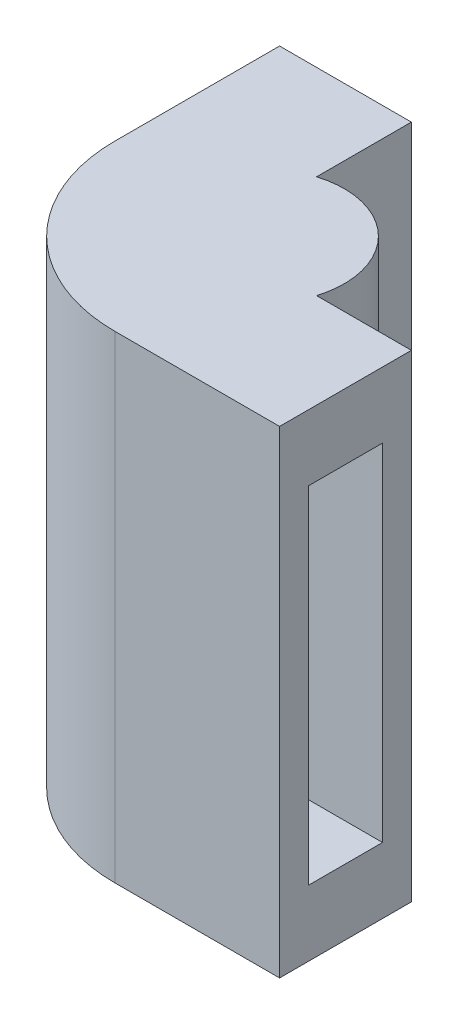
SolidWorks part; units mm, degrees
ref_plane "Front Plane" through (0, 0, 0) normal (0, 0, 1) x (1, 0, 0)
ref_plane "Top Plane" through (0, 0, 0) normal (0, 1, 0) x (1, 0, 0)
ref_plane "Right Plane" through (0, 0, 0) normal (1, 0, 0) x (0, 0, -1)
sketch "Sketch2" plane through (0, 0, 0) normal (0, 1, 0) x (1, 0, 0)
  line L0 (0, 10) -> (0, 20)
  line L1 (0, 20) -> (8, 20)
  line L2 (8, 20) -> (8, 14.2452)
  line L3 (0, 0) -> (22.3158, 22.3158) construction
  line L4 (10, 0) -> (22.3158, 0) construction
  line L5 (18, 8) -> (22.3158, 8) construction
  line L6 (2.9289, 2.9289) -> (9.4645, 9.4645)
  line L7 (9.4645, 9.4645) -> (13, 13)
  arc A0 (2.9289, 2.9289) -> (0, 10) centre (10, 10) cw
  arc A2 (13, 13) -> (8, 14.2452) centre (9.4645, 9.4645) ccw
  point P13 (8, 8)
  dimension "D2" = 10
  dimension "D5" = 10
  dimension "D1" = 8
  dimension "D4" = 20
other "AlignGroup1"
extrude "Boss-Extrude1" add sketch "Sketch2" along normal blind 29
ref_plane "Plane1" through (0, 0, 0) normal (0.7071, 0, 0.7071) x (0.7071, 0, -0.7071)
mirror "Mirror1" about plane through (0, 0, 0) normal (0.7071, 0, 0.7071) of "Boss-Extrude1"
sketch "Sketch3" plane through (0, 0, -20) normal (0, 0, -1) x (-1, 0, 0)
  line L0 (-4, 0) -> (-4, 4) construction
  line L2 (-8, 0) -> (0, 0) construction
  line L3 (-6.25, 4) -> (-6.25, 25)
  line L4 (-6.25, 4) -> (-1.75, 4)
  line L5 (-6.25, 14.5) -> (-1.75, 14.5) construction
  line L6 (-6.25, 25) -> (-1.75, 25)
  line L7 (-1.75, 4) -> (-1.75, 25)
  dimension "D1" = 4
  dimension "D2" = 4.5
extrude "Cut-Extrude1" cut sketch "Sketch3" against normal blind 6
mirror "Mirror2" about plane through (0, 0, 0) normal (0.7071, 0, 0.7071) of "Cut-Extrude1"
